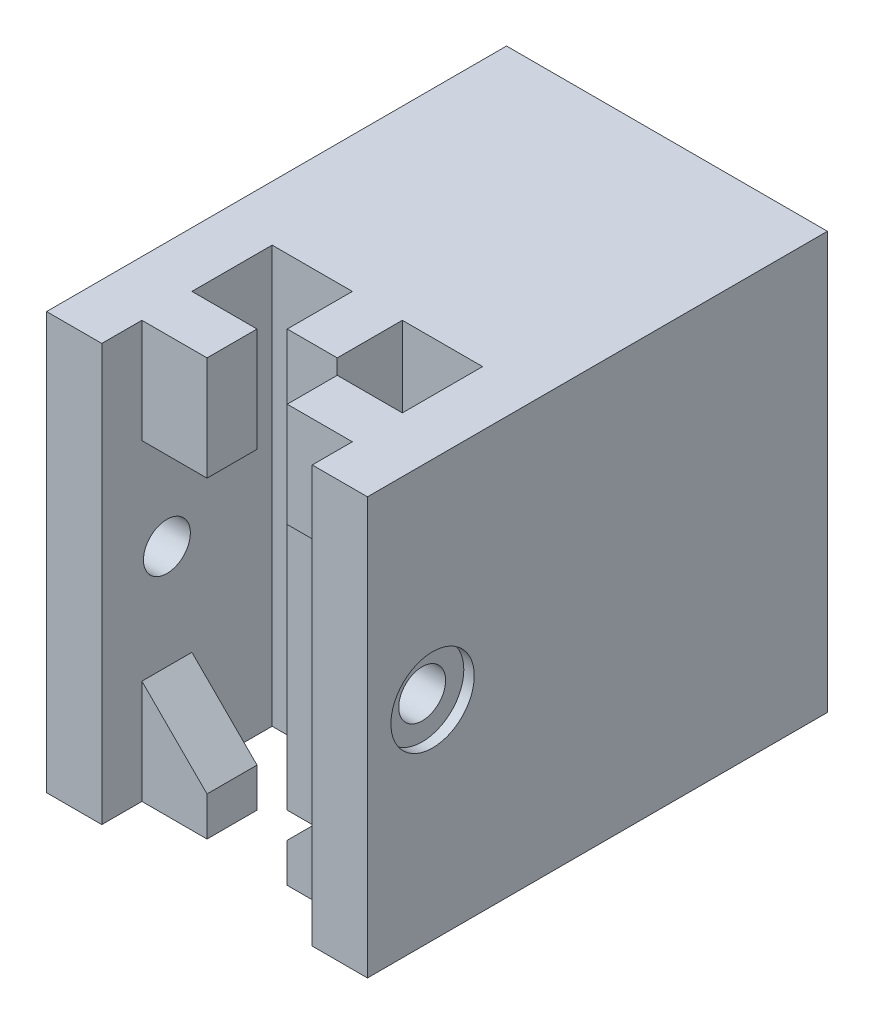
SolidWorks part; units mm, degrees
ref_plane "Plan de face" through (0, 0, 0) normal (0, 0, 1) x (1, 0, 0)
ref_plane "Plan de dessus" through (0, 0, 0) normal (0, 1, 0) x (1, 0, 0)
ref_plane "Plan de droite" through (0, 0, 0) normal (1, 0, 0) x (0, 0, -1)
sketch "Base" plane through (0, 0, 0) normal (0, 1, 0) x (1, 0, 0)
  line L0 (-3.85, -2.4) -> (-3.85, 2.4)
  line L1 (-3.85, 2.4) -> (-10.1, 2.4)
  line L2 (-10.1, 2.4) -> (-10.1, 10.1)
  line L3 (-10.1, 10.1) -> (-2.4, 10.1)
  line L4 (-2.4, 10.1) -> (-2.4, 3.85)
  line L5 (-2.4, 3.85) -> (2.4, 3.85)
  line L6 (0, -55) -> (0, 55) construction
  line L7 (2.4, 10.1) -> (2.4, 3.85)
  line L8 (10.1, 10.1) -> (2.4, 10.1)
  line L9 (10.1, 2.4) -> (10.1, 10.1)
  line L10 (3.85, 2.4) -> (10.1, 2.4)
  line L11 (3.85, -2.4) -> (3.85, 2.4)
  line L12 (-55, 0) -> (55, 0) construction
  line L13 (3.85, -2.4) -> (10.1, -2.4)
  line L14 (10.1, -2.4) -> (10.1, -6.25)
  line L20 (-10.1, -2.4) -> (-10.1, -6.25)
  line L21 (-3.85, -2.4) -> (-10.1, -2.4)
  line L23 (-15.4, 15.4) -> (15.4, 15.4)
  line L24 (-15.4, 15.4) -> (-15.4, -6.25)
  line L26 (15.4, 15.4) -> (15.4, -6.25)
  line L27 (-15.4, 15.4) -> (0, 0) construction
  line L28 (0, 0) -> (15.4, 15.4) construction
  line L29 (-10.1, -6.25) -> (-15.4, -6.25)
  line L30 (10.1, -6.25) -> (15.4, -6.25)
  line L31 (10.1, -10.1) -> (15.4, -15.4) construction
  point P2 (-3.85, 0)
  point P3 (0, 3.85)
  point P27 (0, 0)
  dimension "D1" = 4.8
  dimension "D2" = 4.8
  dimension "D3" = 6.25
  dimension "D4" = 7.7
  dimension "D5" = 30.8
extrude "Boss.-Extru.1" add sketch "Base" along normal mid plane 40
hole_wizard "Chambrage pour vis à six pans creux M41" positions "Esquisse4" profile "Esquisse5" counterbore size "M4" standard "ISO" end condition up to next
sketch "Esquisse4" plane through (15.4, 0, 0) normal (1, 0, 0) x (0, 0, -1)
  point P0 (0, 0)
sketch "Esquisse5" plane through (15.4, 0, 0) normal (0, 1, 0) x (0, 0, -1)
  line L0 (0, 0) -> (0, 11.55)
  line L1 (0, 11.55) -> (2.25, 11.55)
  line L3 (2.25, 11.55) -> (2.25, 1)
  line L4 (2.25, 1) -> (4, 1)
  line L5 (4, 1) -> (4, 0)
  line L7 (4, 0) -> (0, 0)
  line L11 (0, -6.35) -> (0, 107.95) construction
  dimension "Diamètre du perçage jusqu'au prochain" = 4.5
  dimension "Profondeur du perçage jusqu'au prochain" = 11.55
  dimension "Diamètre du chambrage" = 8
  dimension "Profondeur du chambrage" = 1
mirror "Symétrie1" about plane through (0, 0, 0) normal (1, 0, 0) of "Chambrage pour vis à six pans creux M41"
sketch "Esquisse6" plane through (0, 0, 0) normal (0, 0, 1) x (1, 0, 0)
  line L0 (10.1, 20) -> (10.1, -20) construction
  line L1 (-10.1, 10) -> (10.1, 10)
  line L2 (-10.1, 10) -> (-10.1, -10)
  line L3 (-10.1, -10) -> (10.1, -10)
  line L4 (10.1, 10) -> (10.1, -10)
  line L5 (-10.1, 10) -> (10.1, -10) construction
  line L6 (-10.1, -10) -> (10.1, 10) construction
  point P0 (0, 0)
  dimension "D1" = 20
extrude "Enlèv. mat.-Extru.1" cut sketch "Esquisse6" against normal mid plane 6
sketch "Esquisse14" plane through (0, -20, 0) normal (0, -1, 0) x (1, 0, 0)
  line L0 (15.4, 6.25) -> (15.4, -15.4) construction
  line L1 (-15.4, -15.4) -> (15.4, -15.4)
  line L2 (-15.4, -15.4) -> (-15.4, -17.9)
  line L3 (-15.4, -17.9) -> (15.4, -17.9)
  line L4 (15.4, -15.4) -> (15.4, -17.9)
  dimension "D1" = 2.5
extrude "Boss.-Extru.3" add sketch "Esquisse14" against normal up to vertex (40 mm away) up to point (-15.4, 20, -15.4)
chamfer "Chanfrein1" distance 6.25 angle 45 2 edges at (3.85, -10, 0) (-3.85, -10, 0)
sketch "Esquisse15" plane through (0, 0, -17.9) normal (0, 0, -1) x (-1, 0, 0)
  line L1 (-15.4, 20) -> (15.4, 20)
  line L2 (-15.4, 20) -> (-15.4, -20)
  line L3 (-15.4, -20) -> (15.4, -20)
  line L4 (15.4, 20) -> (15.4, -20)
extrude "Boss.-Extru.4" add sketch "Esquisse15" along normal blind 20
sketch "Esquisse17" plane through (-15.4, 0, 0) normal (-1, 0, 0) x (0, 0, 1)
  line L0 (-37.9, -8) -> (-37.9, 8)
  line L1 (-37.9, -20) -> (-37.9, 20) construction
  line L2 (-37.9, 8) -> (-17.9, 15)
  line L3 (-17.9, 15) -> (-17.9, -15)
  line L4 (-17.9, -15) -> (-37.9, -8)
  line L5 (-37.9, -20) -> (6.25, -20) construction
  line L7 (-37.9, 20) -> (6.25, 20) construction
  dimension "D1" = 20
  dimension "D2" = 16
  dimension "D3" = 12
  dimension "D4" = 5
  dimension "D5" = 5
extrude "Enlèv. mat.-Extru.2" cut sketch "Esquisse17" against normal blind 12
